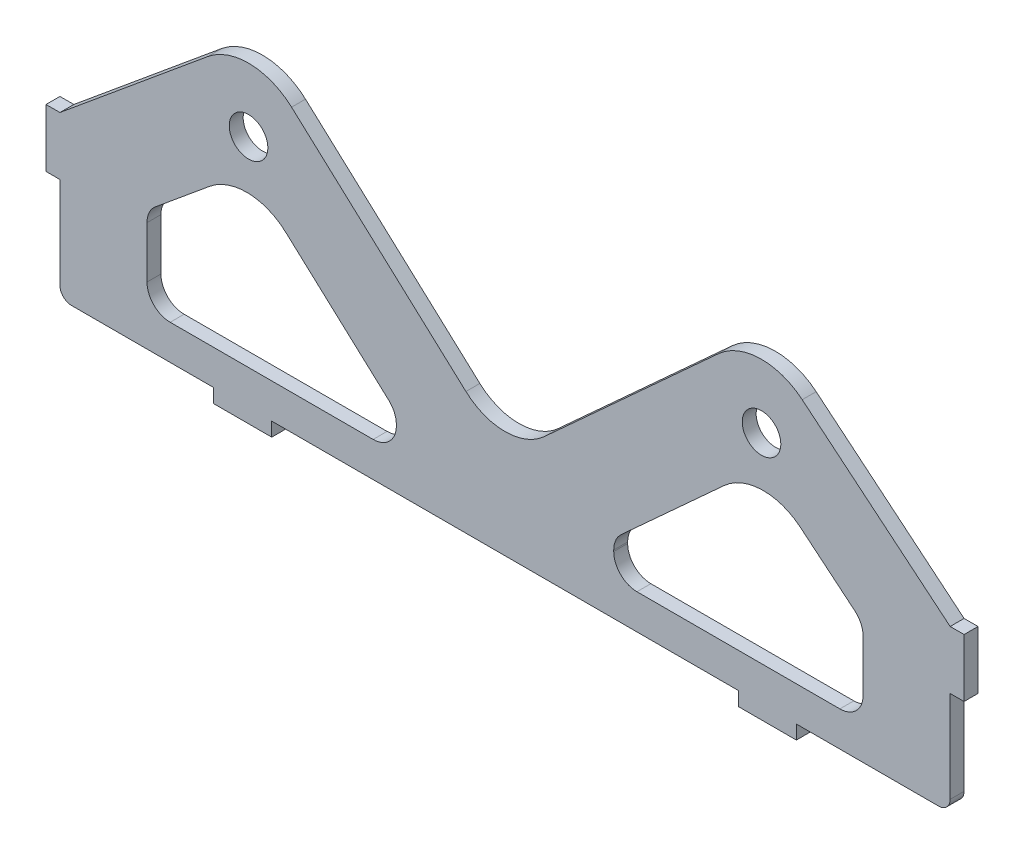
SolidWorks part; units mm, degrees
material "AISI 1020"
ref_plane "Front Plane" through (0, 0, 0) normal (0, 0, 1) x (1, 0, 0)
ref_plane "Top Plane" through (0, 0, 0) normal (0, 1, 0) x (1, 0, 0)
ref_plane "Right Plane" through (0, 0, 0) normal (1, 0, 0) x (0, 0, -1)
sketch "Sketch1" plane through (0, 0, 0) normal (0, 0, 1) x (1, 0, 0)
  line L1 (-97.4016, 35.56) -> (-97.4016, 104.9243) construction
  line L5 (51.054, 0) -> (-51.054, 0)
  line L6 (-51.054, 0) -> (-51.054, -3.048)
  line L7 (-51.054, -3.048) -> (-63.754, -3.048)
  line L8 (-63.754, -3.048) -> (-63.754, 0)
  line L9 (-63.754, 0) -> (-94.8616, 0)
  line L10 (-97.4016, 2.54) -> (-97.4016, 22.606)
  line L11 (-97.4016, 22.606) -> (-100.4496, 22.606)
  line L12 (-100.4496, 22.606) -> (-100.4496, 35.306)
  line L13 (-100.4496, 35.306) -> (-97.4016, 35.306)
  line L15 (-100.4496, 35.56) -> (-100.4496, 104.9243) construction
  line L16 (-64.008, -3.048) -> (-94.7346, -3.048) construction
  line L17 (-97.4016, 35.306) -> (-65.0347, 62.0991)
  line L18 (-46.712, 61.6589) -> (0, 19.05)
  line L19 (-100.4496, 35.56) -> (-97.4016, 35.56) construction
  line L20 (-50.8, -3.048) -> (-50.8, 0) construction
  line L21 (-97.4016, 2.667) -> (-97.4016, 22.352) construction
  line L22 (0, -1000) -> (0, 49000) construction
  line L23 (46.712, 61.6589) -> (0, 19.05)
  line L24 (97.4016, 35.306) -> (65.0347, 62.0991)
  line L25 (100.4496, 35.306) -> (97.4016, 35.306)
  line L26 (100.4496, 22.606) -> (100.4496, 35.306)
  line L27 (97.4016, 22.606) -> (100.4496, 22.606)
  line L28 (97.4016, 2.54) -> (97.4016, 22.606)
  line L29 (63.754, 0) -> (94.8616, 0)
  line L30 (63.754, -3.048) -> (63.754, 0)
  line L31 (51.054, -3.048) -> (63.754, -3.048)
  line L32 (51.054, 0) -> (51.054, -3.048)
  arc A0 (-46.712, 61.6589) -> (-65.0347, 62.0991) centre (-56.1266, 51.3377) ccw
  arc A1 (-94.8616, 0) -> (-97.4016, 2.54) centre (-94.8616, 2.54) cw
  circle A2 centre (56.1266, 51.3377) radius 4.2227
  circle A3 centre (-56.1266, 51.3377) radius 4.2227
  circle A4 centre (-56.1266, 51.3377) radius 4.2227
  arc A5 (94.8616, 0) -> (97.4016, 2.54) centre (94.8616, 2.54) ccw
  arc A6 (46.712, 61.6589) -> (65.0347, 62.0991) centre (56.1266, 51.3377) cw
  point P52 (0, 0)
  dimension "D2" = 27.94
  dimension "D7" = 2.54
  dimension "D1" = 12.7
  dimension "D4" = 19.05
  dimension "D5" = 0.254
  dimension "D6" = 0.254
  dimension "D3" = 0.254
extrude "Boss-Extrude1" add sketch "Sketch1" against normal blind 3.048 contours A2 | A4 | L17 A0 L18 L23 A6 L24 L25 L26 L27 L28 A5 L29 L30 L31 L32 L5 L6 L7 L8 L9 A1 L10 L11 L12 L13 region at (56.1266, 51.3377, 0) region at (-56.1266, 51.3377, 0)
fillet "Fillet1" radius 12.7 1 edges at (0, 19.05, -1.524)
sketch "Sketch3" plane through (0, 0, 0) normal (0, 0, 1) x (1, 0, 0)
  line L0 (-64.629, 37.7048) -> (-78.3516, 26.3453)
  line L1 (-78.3516, 26.3453) -> (-78.3516, 7.62)
  line L2 (-78.3516, 7.62) -> (-23.7825, 7.62)
  line L3 (-23.7825, 7.62) -> (-23.7825, 15.24)
  line L4 (-23.7825, 15.24) -> (-47.972, 37.3047)
  line L5 (-97.4016, 35.306) -> (-65.0347, 62.0991) construction
  line L6 (-46.712, 61.6589) -> (-8.5587, 26.8569) construction
  line L7 (-97.4016, 2.54) -> (-97.4016, 22.606) construction
  line L8 (51.054, 0) -> (-51.054, 0) construction
  arc A0 (-64.629, 37.7048) -> (-47.972, 37.3047) centre (-56.5307, 27.9218) cw
  point P9 (0, 0)
  point P17 (-56.1266, 44.743)
  dimension "D4" = 12.7
  dimension "D1" = 19.05
  dimension "D2" = 19.05
  dimension "D3" = 7.62
  dimension "D5" = 7.62
extrude "Cut-Extrude1" cut sketch "Sketch3" against normal through all both and the other way through all
fillet "Fillet2" radius 5.08 4 edges at (-78.3516, 7.62, -1.524) (-23.7825, 7.62, -1.524) (-23.7825, 15.24, -1.524) (-78.3516, 26.3453, -1.524)
mirror "Mirror1" about plane through (0, 0, 0) normal (1, 0, 0) of "Fillet2", "Cut-Extrude1"
equation "\"D2@Sketch3\"=\"D1@Sketch3\""
